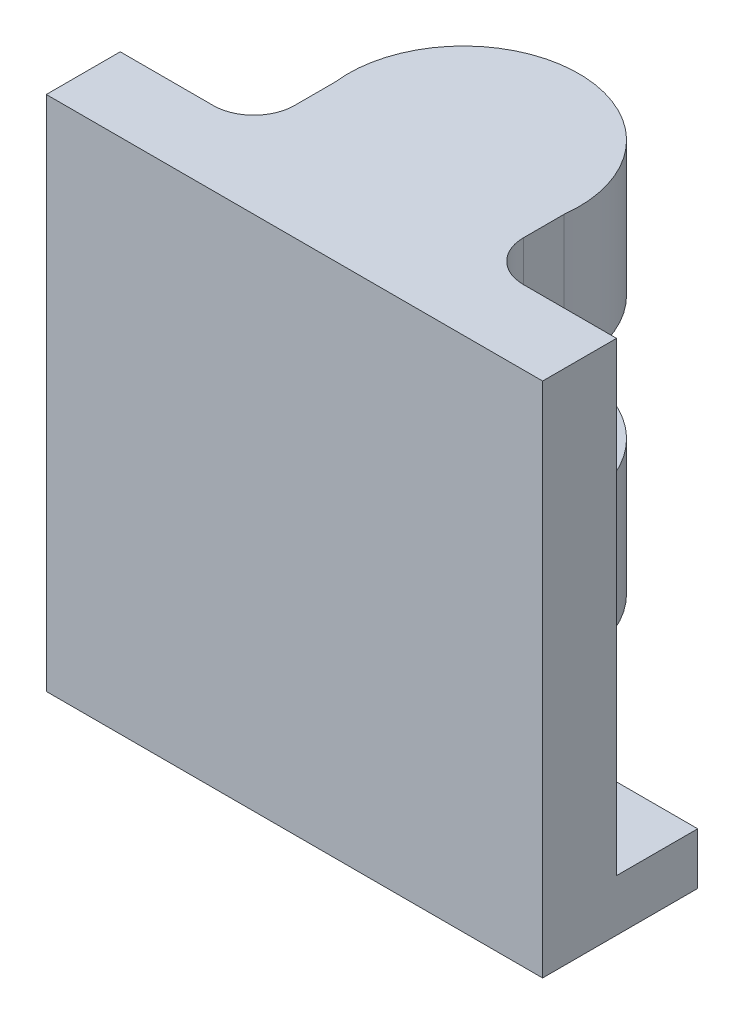
SolidWorks part; units mm, degrees
ref_plane "Front Plane" through (0, 0, 0) normal (0, 0, 1) x (1, 0, 0)
ref_plane "Top Plane" through (0, 0, 0) normal (0, 1, 0) x (1, 0, 0)
ref_plane "Right Plane" through (0, 0, 0) normal (1, 0, 0) x (0, 0, -1)
sketch "Sketch2" plane through (0, 0, 0) normal (0, 1, 0) x (1, 0, 0)
  line L0 (0, 0) -> (0, 321.6826) construction
  line L1 (0, -55) -> (0, 55) construction
  line L2 (-55, 0) -> (55, 0) construction
  line L3 (-30, 129.85) -> (30, 129.85) construction
  line L4 (-48, 134.85) -> (48, 134.85)
  line L5 (-48, 104.85) -> (48, 104.85)
  line L6 (-48, 134.85) -> (-48, 104.85)
  line L7 (48, 134.85) -> (48, 104.85)
  circle A0 centre (0, 0) radius 143.5 construction
  circle A1 centre (0, 0) radius 76.46 construction
  circle A2 centre (30, 127) radius 2.85 construction
  circle A3 centre (-30, 127) radius 2.85 construction
  circle A4 centre (-30, 127) radius 1.5
  circle A5 centre (30, 127) radius 1.5
  dimension "D1" = 287
  dimension "D2" = 30
  dimension "D3" = 127
  dimension "D4" = 152.92
  dimension "D5" = 5.7
  dimension "D10" = 3
  dimension "D6" = 5
  dimension "D7" = 48
  dimension "D8" = 30
  dimension "D9" = 96
extrude "Boss-Extrude2" add sketch "Sketch2" along normal blind 10
sketch "Sketch4" plane through (0, 0, 0) normal (0, 1, 0) x (1, 0, 0)
  line L0 (0, 0) -> (0, 208.8835) construction
  line L1 (0, -55) -> (0, 55) construction
  line L2 (-22.15, 134.85) -> (22.15, 134.85)
  line L3 (22.15, 127) -> (22.15, 134.85)
  line L4 (-48, 134.85) -> (-48, 104.85)
  line L5 (-48, 104.85) -> (48, 104.85)
  line L6 (48, 104.85) -> (48, 134.85)
  line L7 (48, 134.85) -> (-48, 134.85)
  line L8 (-48, 134.85) -> (-48, 104.85) construction
  line L9 (-48, 104.85) -> (48, 104.85) construction
  line L10 (48, 104.85) -> (48, 134.85) construction
  line L11 (48, 134.85) -> (-48, 134.85) construction
  line L12 (30, 119.15) -> (48, 119.15)
  line L13 (48, 119.15) -> (48, 104.85)
  line L14 (48, 104.85) -> (-48, 104.85)
  line L15 (-48, 119.15) -> (-48, 104.85)
  line L16 (-30, 119.15) -> (-48, 119.15)
  line L17 (-22.15, 127) -> (-22.15, 134.85)
  circle A2 centre (-30, 127) radius 1.5 construction
  circle A3 centre (30, 127) radius 1.5 construction
  circle A4 centre (-30, 127) radius 1.5 construction
  circle A5 centre (30, 127) radius 1.5 construction
  circle A6 centre (30, 127) radius 2.85 construction
  circle A7 centre (-30, 127) radius 2.85 construction
  arc A8 (22.15, 127) -> (30, 119.15) centre (30, 127) ccw
  arc A9 (-22.15, 127) -> (-30, 119.15) centre (-30, 127) cw
  point P17 (0, 104.85)
  point P27 (0, 134.85)
  dimension "D2" = 5.7
  dimension "D3" = 5
  dimension "D1" = 0
extrude "Boss-Extrude4" add sketch "Sketch4" along normal blind 100
ref_plane "Plane1" through (0, 100, 0) normal (0, 1, 0) x (1, 0, 0)
sketch "Sketch6" plane through (0, 100, 0) normal (0, 1, 0) x (1, 0, 0)
  line L0 (0, 185.6807) -> (0, 59.5183) construction
  line L1 (0, -5.5) -> (0, 5.5) construction
  line L2 (22.15, 134.85) -> (22.15, 104.85)
  line L3 (22.15, 104.85) -> (-22.15, 104.85)
  line L4 (-22.15, 104.85) -> (-22.15, 134.85)
  line L8 (-48, 119.15) -> (-48, 104.85)
  line L9 (-48, 104.85) -> (48, 104.85)
  line L10 (48, 104.85) -> (48, 119.15)
  line L11 (48, 119.15) -> (30, 119.15)
  line L12 (22.15, 127) -> (22.15, 134.85)
  line L13 (22.15, 134.85) -> (-22.15, 134.85)
  line L14 (-22.15, 134.85) -> (-22.15, 127)
  line L15 (-30, 119.15) -> (-48, 119.15)
  line L16 (-48, 119.15) -> (-48, 104.85) construction
  line L17 (-48, 104.85) -> (48, 104.85) construction
  line L18 (48, 104.85) -> (48, 119.15) construction
  line L19 (48, 119.15) -> (30, 119.15) construction
  line L20 (22.15, 127) -> (22.15, 134.85) construction
  line L21 (22.15, 134.85) -> (-22.15, 134.85) construction
  line L22 (-22.15, 134.85) -> (-22.15, 127) construction
  line L23 (-30, 119.15) -> (-48, 119.15) construction
  arc A1 (22.15, 134.85) -> (-22.15, 134.85) centre (0, 137.5375) ccw
  arc A2 (22.15, 127) -> (30, 119.15) centre (30, 127) ccw
  arc A3 (-30, 119.15) -> (-22.15, 127) centre (-30, 127) ccw
  arc A4 (22.15, 127) -> (30, 119.15) centre (30, 127) ccw construction
  arc A5 (-30, 119.15) -> (-22.15, 127) centre (-30, 127) ccw construction
  point P7 (0, 159.85)
  point P15 (0, 134.85)
  dimension "D2" = 25
  dimension "D1" = 0
extrude "Boss-Extrude5" add sketch "Sketch6" against normal blind 26
ref_axis "Axis1" through (0, -5, 0) along (0, 1, 0)
pattern_linear "LPattern1" count 2 spacing 50 along (0, -1, 0) of "Boss-Extrude5"
sketch "Sketch8" plane through (0, 0, 0) normal (1, 0, 0) x (0, 0, -1)
  line L0 (104.85, 0) -> (134.85, 0) construction
  line L1 (134.85, 0) -> (134.85, 10) construction
  line L2 (134.85, 10) -> (119.15, 10) construction
  line L3 (119.15, 10) -> (119.15, 100) construction
  line L4 (119.15, 100) -> (104.85, 100) construction
  line L5 (104.85, 100) -> (104.85, 0) construction
  line L6 (159.85, 50) -> (134.85, 50) construction
  line L7 (134.85, 50) -> (134.85, 24) construction
  line L8 (134.85, 24) -> (159.85, 24) construction
  line L9 (134.85, 24) -> (134.85, 50) construction
  line L10 (159.85, 100) -> (134.85, 100) construction
  line L11 (134.85, 100) -> (134.85, 74) construction
  line L12 (134.85, 74) -> (159.85, 74) construction
  line L13 (134.85, 74) -> (134.85, 100) construction
  line L14 (104.85, 0) -> (134.85, 0) construction
  line L15 (134.85, 0) -> (134.85, 10) construction
  line L16 (134.85, 10) -> (119.15, 10) construction
  line L17 (119.15, 10) -> (119.15, 100) construction
  line L18 (119.15, 100) -> (104.85, 100) construction
  line L19 (104.85, 100) -> (104.85, 0) construction
  line L20 (159.85, 50) -> (134.85, 50) construction
  line L21 (134.85, 50) -> (134.85, 24) construction
  line L22 (134.85, 24) -> (159.85, 24) construction
  line L23 (134.85, 24) -> (134.85, 50) construction
  line L24 (159.85, 100) -> (134.85, 100) construction
  line L25 (134.85, 100) -> (134.85, 74) construction
  line L26 (134.85, 74) -> (159.85, 74) construction
  line L27 (134.85, 74) -> (134.85, 100) construction
  line L28 (159.85, 100) -> (159.85, 24) construction
  line L29 (159.85, 74) -> (120.5531, 74)
  line L30 (120.5531, 74) -> (114.3364, 50)
  line L31 (114.3364, 50) -> (159.85, 50)
